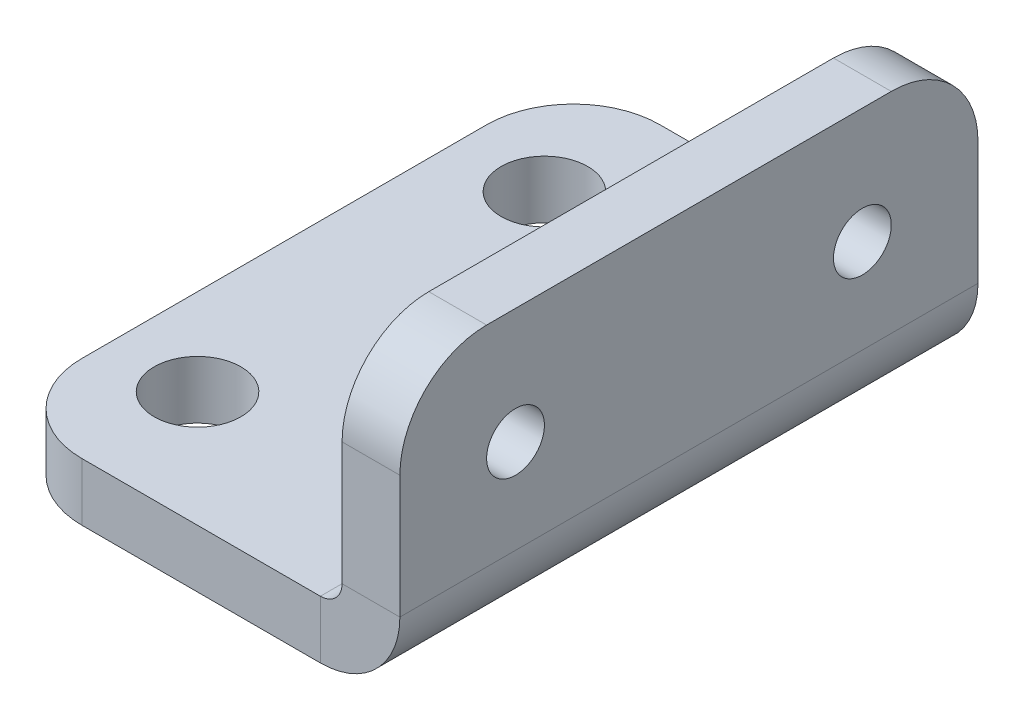
SolidWorks part; units mm, degrees
note: The reader was unsure of these and kept them because the rebuilt part matched: bend radius of "BaseBend1".
ref_plane "Front Plane" through (0, 0, 0) normal (0, 0, 1) x (1, 0, 0)
ref_plane "Top Plane" through (0, 0, 0) normal (0, 1, 0) x (1, 0, 0)
ref_plane "Right Plane" through (0, 0, 0) normal (1, 0, 0) x (0, 0, -1)
sketch "Sketch1" plane through (0, 0, 0) normal (0, 0, 1) x (1, 0, 0)
  line L0 (-12, 0) -> (0, 0)
  line L1 (0, 0) -> (0, 8)
  dimension "D1" = 8
  dimension "D2" = 12
base flange "Base-Flange1" sketch "Sketch1" end condition mid plane depth 20 reverse direction no thickness 2 reverse thickness direction no bend radius 0.75
bend "BaseBend1" bend radius 0.75 bend angle 90 parameters "D5"=1
fillet "Fillet1" radius 3 4 edges at (-12, -1, 10) (-12, -1, -10) (1, 8, -10) (1, 8, 10)
sketch "Sketch6" plane through (0, 0, 0) normal (0, 1, 0) x (1, 0, 0)
  line L0 (-12, -7) -> (-12, 7) construction
  line L1 (0, 0) -> (-12, 0) construction
  circle A0 centre (-9, 6) radius 1.5
  circle A1 centre (-9, -6) radius 1.5
  dimension "D2" = 3
  dimension "D1" = 3
  dimension "D3" = 6
extrude "Cut-Extrude1" cut sketch "Sketch6" against normal through all normal cut yes
sketch "Sketch11" plane through (0, 0, 0) normal (-1, 0, 0) x (0, 0, 1)
  line L0 (10, 0.75) -> (10, 5) construction
  line L2 (10, -2) -> (-10, -2) construction
  circle A0 centre (6, 4) radius 1
  circle A1 centre (-6, 4) radius 1
  dimension "D1" = 2
  dimension "D2" = 4
  dimension "D3" = 6
extrude "Cut-Extrude2" cut sketch "Sketch11" against normal blind 2 normal cut yes
sketch "Bend-Lines1" [suppressed] plane through (0, 0, 0) normal (0, 1, 0) x (1, 0, 0)
sketch "Bounding-Box1" [suppressed] plane through (0, 0, 0) normal (0, 1, 0) x (1, 0, 0)
sheet metal parameters "Sheet-Metal1" thickness 2 parameters "D1"=0.75
flat pattern "Flat-Pattern1" [suppressed]
sketch "Bend-Lines2" plane through (0, 0, 0) normal (0, 1, 0) x (1, 0, 0)
  line L0 (0.436, 10) -> (0.436, -10) construction
  line L1 (0.436, 10) -> (0.436, -10) construction
sketch3d "Bounding-Box2" [suppressed]
  line L0 (0, 0, 0) -> (20.8719, 0, 0) construction
  line L1 (0, 20, 0) -> (20.8719, 20, 0) construction
  line L2 (0, 0, 0) -> (0, 20, 0) construction
  line L3 (20.8719, 0, 0) -> (20.8719, 20, 0) construction
bend of the flat pattern "Flatten-<BaseBend1>1"
sheet metal parameters "Sheet-Metal2" thickness 2 parameters "D1"=0.75
flat pattern "Flat-Pattern1"
sketch "Bend-Lines2" plane through (0, 0, 0) normal (0, 1, 0) x (1, 0, 0)
  line L0 (0.436, 10) -> (0.436, -10) construction
  line L1 (0.436, 10) -> (0.436, -10) construction
sketch3d "Bounding-Box2" [suppressed]
  line L0 (0, 0, 0) -> (20.8719, 0, 0) construction
  line L1 (0, 20, 0) -> (20.8719, 20, 0) construction
  line L2 (0, 0, 0) -> (0, 20, 0) construction
  line L3 (20.8719, 0, 0) -> (20.8719, 20, 0) construction
bend of the flat pattern "Flatten-<BaseBend1>1"
sheet metal parameters "Sheet-Metal4" thickness 2 parameters "D1"=0.75
flat pattern "Flat-Pattern1"
sketch "Bend-Lines2" plane through (0, 0, 0) normal (0, 1, 0) x (1, 0, 0)
  line L0 (0.436, 10) -> (0.436, -10) construction
  line L1 (0.436, 10) -> (0.436, -10) construction
sketch3d "Bounding-Box2" [suppressed]
  line L0 (0, 0, 0) -> (20.8719, 0, 0) construction
  line L1 (0, 20, 0) -> (20.8719, 20, 0) construction
  line L2 (0, 0, 0) -> (0, 20, 0) construction
  line L3 (20.8719, 0, 0) -> (20.8719, 20, 0) construction
bend of the flat pattern "Flatten-<BaseBend1>1"
